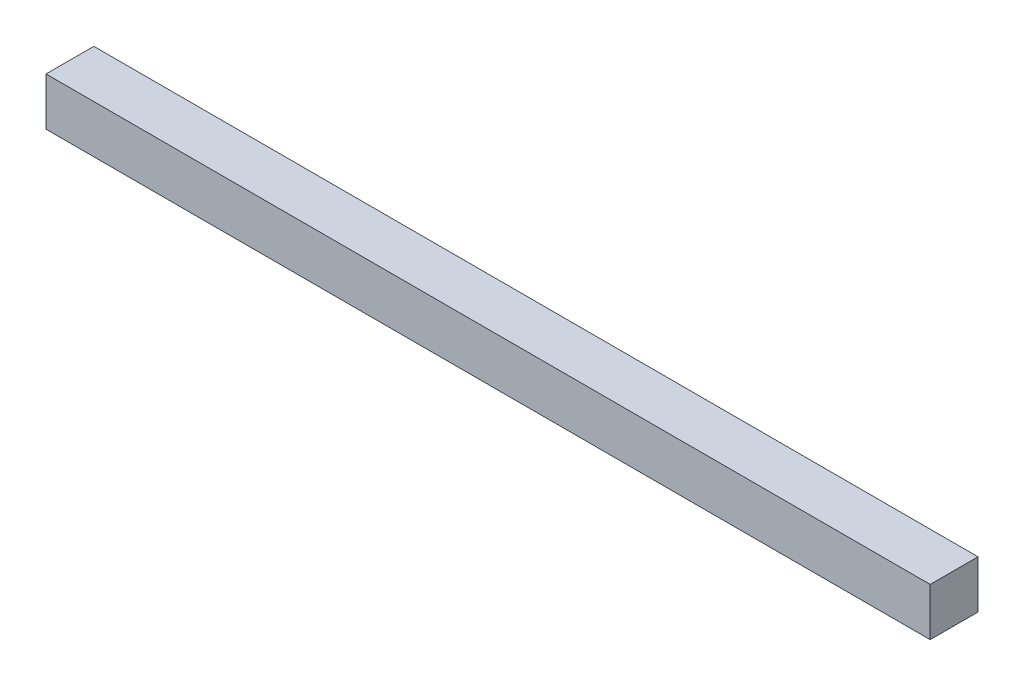
SolidWorks part; units mm, degrees
ref_plane "Front Plane" through (0, 0, 0) normal (0, 0, 1) x (1, 0, 0)
ref_plane "Top Plane" through (0, 0, 0) normal (0, 1, 0) x (1, 0, 0)
ref_plane "Right Plane" through (0, 0, 0) normal (1, 0, 0) x (0, 0, -1)
sketch "Sketch1" plane through (0, 0, 0) normal (0, 1, 0) x (1, 0, 0)
  line L1 (0, 0) -> (-58.674, 0)
  line L2 (0, 0) -> (0, 3.175)
  line L3 (0, 3.175) -> (-58.674, 3.175)
  line L4 (-58.674, 0) -> (-58.674, 3.175)
  dimension "D1" = 58.674
  dimension "D2" = 3.175
extrude "Boss-Extrude1" add sketch "Sketch1" along normal blind 3.175
